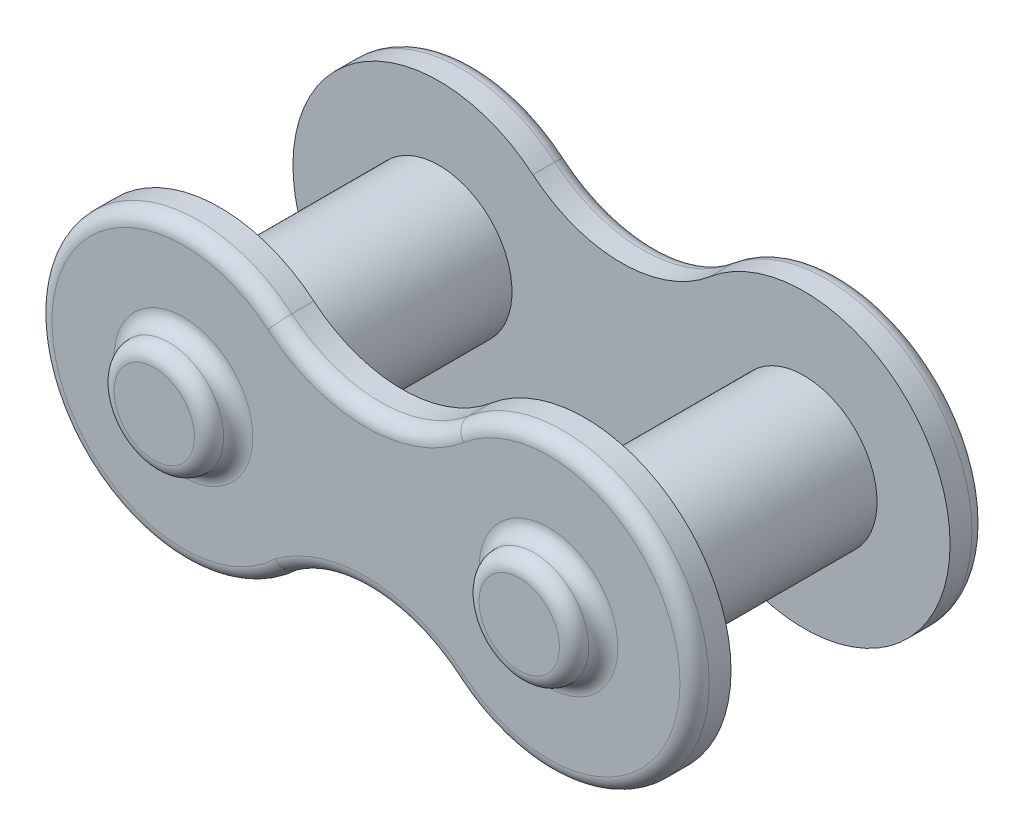
SolidWorks part; units mm, degrees
ref_plane "Front Plane" through (0, 0, 0) normal (0, 0, 1) x (1, 0, 0)
ref_plane "Top Plane" through (0, 0, 0) normal (0, 1, 0) x (1, 0, 0)
ref_plane "Right Plane" through (0, 0, 0) normal (1, 0, 0) x (0, 0, -1)
sketch "Sketch1" plane through (0, 0, 0) normal (0, 0, 1) x (1, 0, 0)
  line L0 (-25.6741, -9.9145) -> (-16.7579, -9.9145) construction
  arc A0 (-26.1918, -6.0371) -> (-25.9464, -13.599) centre (-29.4579, -9.9281) ccw
  arc A1 (-20.0323, -13.7984) -> (-20.0323, -6.0305) centre (-16.7579, -9.9145) ccw
  arc A2 (-26.1918, -6.0371) -> (-20.0323, -6.0305) centre (-23.116, -2.3728) ccw
  arc A3 (-25.9464, -13.599) -> (-20.0323, -13.7984) centre (-23.116, -17.4561) cw
  dimension "D1" = 10.16
  dimension "D2" = 10.16
  dimension "D3" = 12.7
extrude "Boss-Extrude1" add sketch "Sketch1" along normal blind 1.27
sketch "Sketch2" plane through (0, 0, 1.27) normal (0, 0, 1) x (1, 0, 0)
  circle A0 centre (-16.7579, -9.9145) radius 2.54
  circle A1 centre (-29.4579, -9.9281) radius 2.54
  dimension "D1" = 5.08
extrude "Boss-Extrude2" add sketch "Sketch2" along normal blind 7.62
ref_plane "Plane1" through (0, 0, 5.08) normal (0, 0, 1) x (1, 0, 0)
mirror "Mirror1" about plane through (0, 0, 5.08) normal (0, 0, 1) of "Boss-Extrude1"
sketch "Sketch3" plane through (0, 0, 0) normal (0, 0, -1) x (-1, 0, 0)
  circle A0 centre (29.4579, -9.9281) radius 1.905
  circle A1 centre (16.7579, -9.9145) radius 1.905
  dimension "D1" = 3.81
extrude "Boss-Extrude3" add sketch "Sketch3" along normal blind 1.016
fillet "Fillet1" radius 0.508 2 edges at (-31.3629, -9.9281, -1.016) (-18.6629, -9.9145, -1.016)
fillet "Fillet2" radius 0.508 10 edges at (-34.5352, -10.0929, 10.16) (-23.1109, -7.157, 10.16) (-11.6779, -9.9145, 10.16) (-22.9548, -12.6746, 10.16) (-18.6629, -9.9145, 0) (-11.6779, -9.9145, 0) (-23.1109, -7.157, 0) (-34.5352, -10.0929, 0) (-22.9548, -12.6746, 0) (-31.3629, -9.9281, 0)
mirror "Mirror3" about plane through (0, 0, 5.08) normal (0, 0, 1) of "Fillet1", "Fillet2", "Boss-Extrude3"
